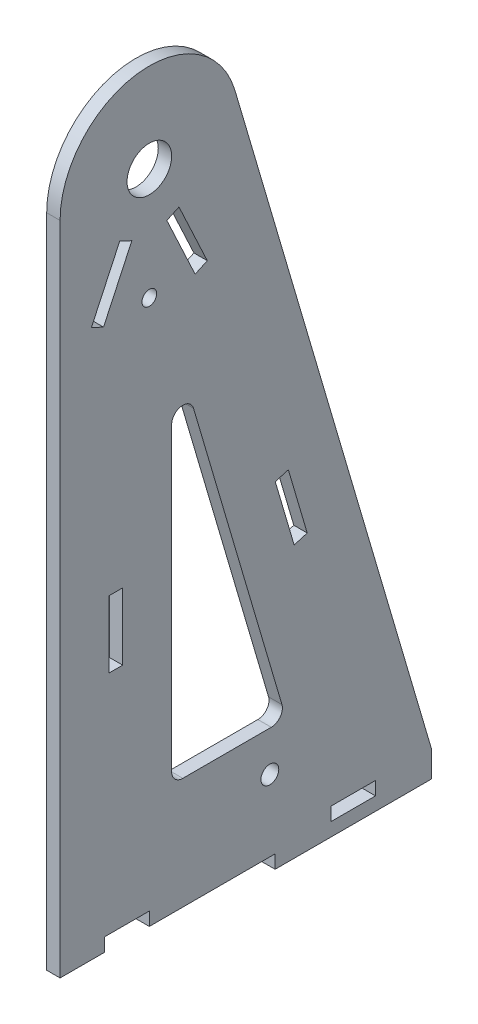
SolidWorks part; units mm, degrees
other "Markup1"
sketch "Sketch3" plane through (3, -150, -63.1818) normal (1, 0, 0) x (0, 0, -1)
ref_plane "Front Plane" through (0, 0, 0) normal (0, 0, 1) x (1, 0, 0)
ref_plane "Top Plane" through (0, 0, 0) normal (0, 1, 0) x (1, 0, 0)
ref_plane "Right Plane" through (0, 0, 0) normal (1, 0, 0) x (0, 0, -1)
sketch "Sketch1" plane through (0, 0, 0) normal (1, 0, 0) x (0, 0, -1)
  line L0 (-20, -147) -> (-20, 0)
  line L1 (63.1818, -144) -> (19.1879, 5.6412)
  line L3 (5, -34.7339) -> (5, -122)
  line L4 (5, -122) -> (30.6558, -122)
  line L5 (30.6558, -122) -> (5, -34.7339)
  line L6 (5, -34.7339) -> (28.9849, -27.6824) construction
  line L7 (5, -34.7339) -> (-20, -34.7339) construction
  line L8 (5, -122) -> (5, -147) construction
  line L9 (-20, -147) -> (63.1818, -147)
  line L10 (63.1818, -147) -> (63.1818, -144)
  line L11 (0, 0) -> (8.4524, -18.1262) construction
  line L12 (0, 0) -> (-8.4524, -18.1262) construction
  line L13 (10.2625, -25.5574) -> (3.9233, -11.9628)
  line L14 (10.2625, -25.5574) -> (12.9815, -24.2895)
  line L15 (3.9233, -11.9628) -> (6.6422, -10.6949)
  line L16 (12.9815, -24.2895) -> (6.6422, -10.6949)
  line L17 (10.2625, -25.5574) -> (6.6422, -10.6949) construction
  line L18 (3.9233, -11.9628) -> (12.9815, -24.2895) construction
  line L19 (-12.9815, -24.2895) -> (-6.6422, -10.6949)
  line L20 (-12.9815, -24.2895) -> (-10.2625, -25.5574)
  line L21 (-6.6422, -10.6949) -> (-3.9233, -11.9628)
  line L22 (-10.2625, -25.5574) -> (-3.9233, -11.9628)
  line L23 (-12.9815, -24.2895) -> (-3.9233, -11.9628) construction
  line L24 (-6.6422, -10.6949) -> (-10.2625, -25.5574) construction
  line L25 (0, 0) -> (0, -25) construction
  circle A0 centre (0, 0) radius 5
  arc A1 (-20, 0) -> (19.1879, 5.6412) centre (0, 0) cw
  circle A2 centre (0, -25) radius 1.65
  point P18 (-5.2827, -11.3288)
  point P19 (5.2827, -11.3288)
  dimension "D1" = 10
  dimension "D2" = 15
  dimension "D3" = 144
  dimension "D7" = 3.3
  dimension "D4" = 16.383
  dimension "D5" = 25
  dimension "D6" = 3
  dimension "D8" = 25
  dimension "D9" = 3
  dimension "D10" = 15
  dimension "D11" = 25
  dimension "D12" = 25
  dimension "D13" = 20
extrude "Boss-Extrude1" add sketch "Sketch1" along normal blind 3
fillet "Fillet1" radius 2.5 3 edges at (1.5, -34.7339, -5) (1.5, -122, -30.6558) (1.5, -122, -5)
sketch "Sketch2" plane through (3, 0, 0) normal (1, 0, 0) x (0, 0, -1)
  line L5 (-20, -147) -> (63.1818, -147) construction
  line L6 (40.6818, -144) -> (50.6818, -144)
  line L7 (40.6818, -144) -> (40.6818, -147)
  line L12 (40.6818, -147) -> (50.6818, -147)
  line L13 (50.6818, -144) -> (50.6818, -147)
  line L14 (40.6818, -144) -> (50.6818, -147) construction
  line L15 (40.6818, -147) -> (50.6818, -144) construction
  line L19 (63.1818, -147) -> (63.1818, -150)
  line L20 (-10, -144) -> (0, -144)
  line L21 (-10, -144) -> (-10, -147)
  line L22 (-10, -147) -> (0, -147)
  line L23 (0, -144) -> (0, -147)
  line L24 (-10, -144) -> (0, -147) construction
  line L25 (-10, -147) -> (0, -144) construction
  line L26 (63.1818, -150) -> (28.1818, -150)
  line L27 (28.1818, -150) -> (28.1818, -147)
  line L28 (-20, 0) -> (-20, -147) construction
  point P0 (45.6818, -145.5)
  point P7 (-5, -145.5)
  point P15 (45.6818, -150)
  line M20 (-20, -147) -> (63.1818, -147)
  dimension "D1" = 3
  dimension "D2" = 35
  dimension "D3" = 10
  dimension "D4" = 10
  dimension "D5" = 10
extrude "Cut-Extrude1" cut sketch "Sketch2" against normal through all both and the other way through all contours L13 L6 L7 M20 | L23 L20 L21 M20 region at (3, -145.5, 5) region at (3, -145.5, -45.6818)
extrude "Boss-Extrude2" add sketch "Sketch2<3>" against normal blind 3 contours L27 L26 L19 M20 region at (3, -148.5, -45.6818)
sketch "Sketch2<3>" plane through (3, 0, 0) normal (1, 0, 0) x (0, 0, -1) same geometry as "Sketch2"
sketch "Sketch4" plane through (3, 0, 0) normal (1, 0, 0) x (0, 0, -1)
  line L0 (32.4508, -89.1952) -> (28.22, -74.8042)
  line L1 (-9.025, -93.3004) -> (-5.975, -93.3004)
  line L2 (-9.025, -93.3004) -> (-9.025, -78.3004)
  line L3 (-9.025, -78.3004) -> (-5.975, -78.3004)
  line L4 (-5.975, -93.3004) -> (-5.975, -78.3004)
  line L5 (-9.025, -93.3004) -> (-5.975, -78.3004) construction
  line L6 (-9.025, -78.3004) -> (-5.975, -93.3004) construction
  line L7 (32.4508, -89.1952) -> (35.377, -88.3349)
  line L8 (28.22, -74.8042) -> (31.1461, -73.9439)
  line L9 (35.377, -88.3349) -> (31.1461, -73.9439)
  line L10 (32.4508, -89.1952) -> (31.1461, -73.9439) construction
  line L11 (28.22, -74.8042) -> (35.377, -88.3349) construction
  line L12 (63.1818, -144) -> (19.1879, 5.6412) construction
  line L13 (-20, -85.8004) -> (5, -85.8004) construction
  line L14 (-20, 0) -> (-20, -147) construction
  line L15 (5, -52.1008) -> (5, -119.5) construction
  line L16 (19.806, -85.0953) -> (43.791, -78.0438) construction
  line L17 (29.7135, -118.7949) -> (9.8985, -51.3957) construction
  line L18 (7.5, -122) -> (27.3151, -122) construction
  circle A0 centre (27, -131) radius 2
  point P0 (-7.5, -85.8004)
  point P6 (31.7985, -81.5695)
  point P22 (31.7985, -81.5695)
  point P23 (-7.5, -85.8004)
  point P24 (5, -85.8004)
  point P25 (19.806, -85.0953)
  dimension "D3" = 4
  dimension "D1" = 3.05
  dimension "D2" = 15
  dimension "D4" = 9
  dimension "D5" = 22
extrude "Cut-Extrude2" cut sketch "Sketch4" against normal through all both and the other way through all
